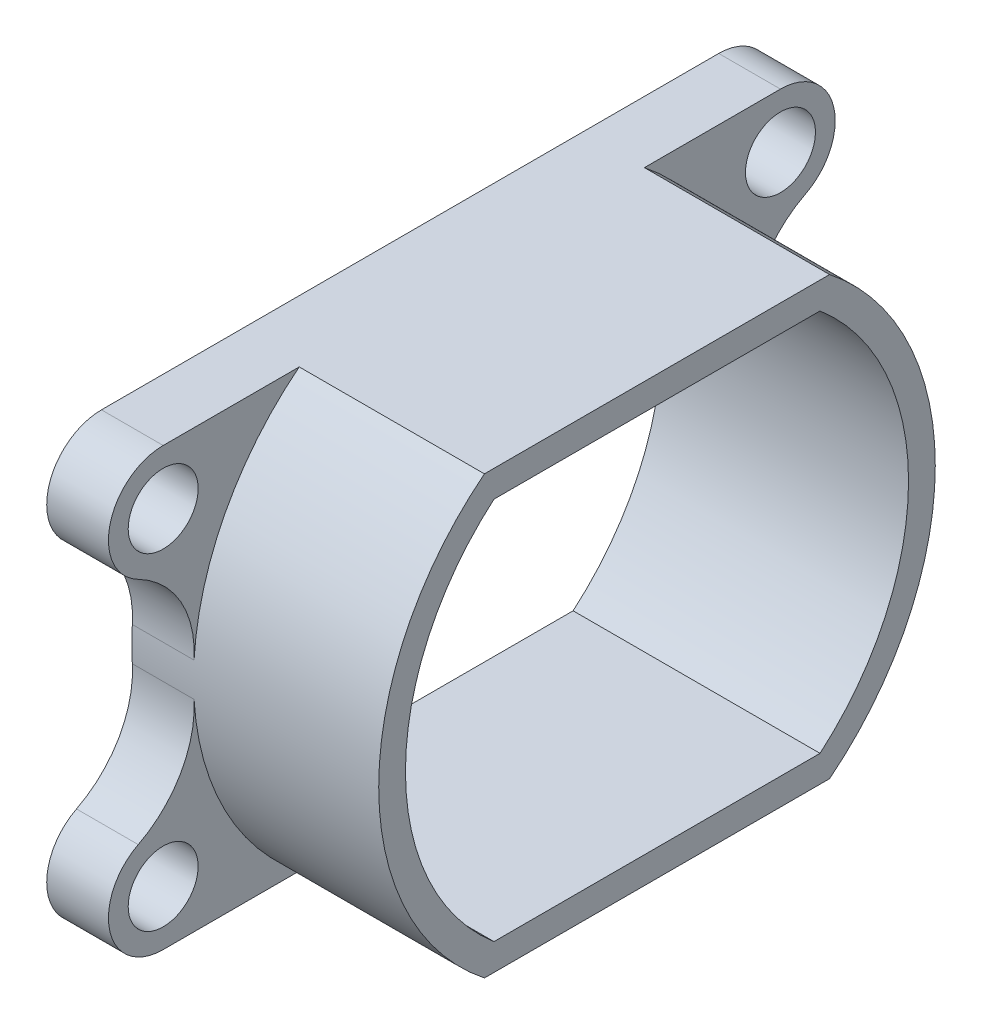
SolidWorks part; units mm, degrees
ref_plane "Front Plane" through (0, 0, 0) normal (0, 0, 1) x (1, 0, 0)
ref_plane "Top Plane" through (0, 0, 0) normal (0, 1, 0) x (1, 0, 0)
ref_plane "Right Plane" through (0, 0, 0) normal (1, 0, 0) x (0, 0, -1)
sketch "Sketch1" plane through (0, 0, 0) normal (1, 0, 0) x (0, 0, -1)
  line L0 (-7.8677, -9.16) -> (7.8677, -9.16) construction
  line L1 (-7.8677, 9.16) -> (7.8677, 9.16) construction
  line L2 (-7.8677, -9.16) -> (7.8677, 9.16) construction
  line L3 (-7.8677, 9.16) -> (7.8677, -9.16) construction
  line L4 (-7.923, 9.31) -> (7.923, 9.31)
  line L5 (-7.923, -9.31) -> (7.923, -9.31)
  line L6 (-8.3877, 10.61) -> (8.3877, 10.61)
  line L7 (-8.3877, -10.61) -> (8.3877, -10.61)
  arc A0 (-7.8677, 9.16) -> (-7.8677, -9.16) centre (0, 0) ccw construction
  arc A1 (7.8677, -9.16) -> (7.8677, 9.16) centre (0, 0) ccw construction
  arc A2 (7.923, -9.31) -> (7.923, 9.31) centre (0, 0) ccw
  arc A3 (-7.923, 9.31) -> (-7.923, -9.31) centre (0, 0) ccw
  arc A4 (8.3877, -10.61) -> (8.3877, 10.61) centre (0, 0) ccw
  arc A5 (-8.3877, 10.61) -> (-8.3877, -10.61) centre (0, 0) ccw
  point P0 (0, 0)
  dimension "D2" = 24.15
  dimension "D1" = 18.32
  dimension "D3" = 0.15
  dimension "D4" = 1.3
extrude "Motor Holder" add sketch "Sketch1" along normal blind 12
sketch "Sketch2" plane through (0, 0, 0) normal (-1, 0, 0) x (0, 0, 1)
  line L4 (0, 0) -> (0, 27.8421) construction
  line L5 (0, 0) -> (-9.5877, 0) construction
  line L7 (8.3877, 10.61) -> (15, 10.61)
  line L24 (15.862, 5.4335) -> (12.7951, 4.383)
  line L25 (15.862, -5.4335) -> (12.7951, -4.383)
  line L26 (8.3877, -10.61) -> (15, -10.61)
  line L27 (-8.3877, -10.61) -> (-15, -10.61)
  line L28 (-15.862, -5.4335) -> (-12.7951, -4.383)
  line L29 (-15.862, 5.4335) -> (-12.7951, 4.383)
  line L30 (-8.3877, 10.61) -> (-15, 10.61)
  circle A10 centre (15, 7.95) radius 1.7
  circle A12 centre (-15, 7.95) radius 1.7
  circle A13 centre (15, -7.95) radius 1.7
  circle A14 centre (-15, -7.95) radius 1.7
  arc A16 (-8.3877, 10.61) -> (-8.3877, -10.61) centre (0, 0) ccw construction
  arc A20 (15, 10.61) -> (15.862, 5.4335) centre (15, 7.95) cw
  arc A21 (8.3877, 10.61) -> (12.7951, 4.383) centre (0, 0) cw
  arc A22 (-8.3877, 10.61) -> (-8.3877, -10.61) centre (0, 0) ccw
  arc A31 (-8.3877, 10.61) -> (-8.3877, -10.61) centre (0, 0) ccw
  arc A32 (8.3877, -10.61) -> (8.3877, 10.61) centre (0, 0) ccw construction
  arc A33 (15, -10.61) -> (15.862, -5.4335) centre (15, -7.95) ccw
  arc A34 (8.3877, -10.61) -> (12.7951, -4.383) centre (0, 0) ccw
  arc A35 (-8.3877, -10.61) -> (-12.7951, -4.383) centre (0, 0) cw
  arc A36 (-15, -10.61) -> (-15.862, -5.4335) centre (-15, -7.95) cw
  arc A37 (-15, 10.61) -> (-15.862, 5.4335) centre (-15, 7.95) ccw
  arc A38 (-8.3877, 10.61) -> (-12.7951, 4.383) centre (0, 0) ccw
  arc M11 (8.3877, -10.61) -> (8.3877, 10.61) centre (0, 0) ccw
  arc M13 (-8.3877, 10.61) -> (-8.3877, -10.61) centre (0, 0) ccw
  dimension "D2" = 3.4
  dimension "D1" = 7.95
  dimension "D3" = 15
extrude "Boss-Extrude1" add sketch "Sketch2" against normal blind 3 contours L30 A37 L29 A12 M13 | A36 L27 L28 A14 M13 | L26 A33 L25 A13 M11 | A20 L7 L24 A10 M11 region at (0, -5.0139, 14.2924) region at (0, 10.4983, 11.6939) region at (0, 5.0139, -14.2924) region at (0, -10.4983, -11.6939)
fillet "Fillet1" radius 5 4 edges at (1.5, -4.383, -12.7951) (1.5, 4.383, -12.7951) (1.5, -4.383, 12.7951) (1.5, 4.383, 12.7951)
